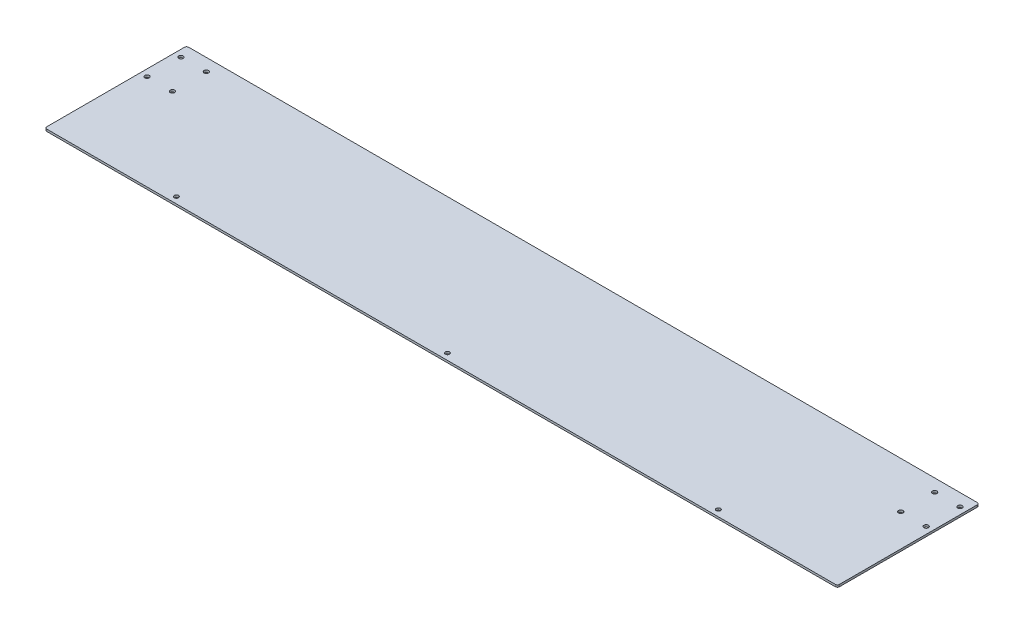
SolidWorks part; units mm, degrees
material "PC High Viscosity"
ref_plane "Front Plane" through (0, 0, 0) normal (0, 0, 1) x (1, 0, 0)
ref_plane "Top Plane" through (0, 0, 0) normal (0, 1, 0) x (1, 0, 0)
ref_plane "Right Plane" through (0, 0, 0) normal (1, 0, 0) x (0, 0, -1)
sketch "Sketch1" plane through (0, 0, 0) normal (0, 1, 0) x (1, 0, 0)
  line L1 (-591.185, -106.3625) -> (591.185, -106.3625)
  line L2 (-594.36, -103.1875) -> (-594.36, 103.1875)
  line L3 (-591.185, 106.3625) -> (591.185, 106.3625)
  line L4 (594.36, -103.1875) -> (594.36, 103.1875)
  line L5 (-594.36, -106.3625) -> (594.36, 106.3625) construction
  line L6 (-594.36, 106.3625) -> (594.36, -106.3625) construction
  arc A0 (591.185, 106.3625) -> (594.36, 103.1875) centre (591.185, 103.1875) cw
  arc A1 (591.185, -106.3625) -> (594.36, -103.1875) centre (591.185, -103.1875) ccw
  arc A2 (-591.185, -106.3625) -> (-594.36, -103.1875) centre (-591.185, -103.1875) cw
  arc A3 (-594.36, 103.1875) -> (-591.185, 106.3625) centre (-591.185, 103.1875) cw
  point P0 (0, 0)
  dimension "D3" = 3.175
  dimension "D1" = 1188.72
  dimension "D2" = 212.725
extrude "Boss-Extrude1" add sketch "Sketch1" along normal blind 3.175
sketch "Sketch2" plane through (0, 3.175, 0) normal (0, 1, 0) x (1, 0, 0)
  line L2 (-406.4, -96.8375) -> (406.4, -96.8375) construction
  line L3 (-591.185, -106.3625) -> (591.185, -106.3625) construction
  point P2 (0, -96.8375)
  point P12 (0, -96.8375)
  dimension "D1" = 812.8
  dimension "D3" = 9.525
hole_wizard "1/4 (0.25) Diameter Hole1" positions "Sketch3" profile "Sketch4" hole size "1/4" standard "ANSI Inch" end condition through all
sketch "Sketch3" plane through (0, 3.175, 0) normal (0, 1, 0) x (1, 0, 0)
  point P9 (0, -96.8375)
  point P28 (-406.4, -96.8375)
  point P31 (406.4, -96.8375)
sketch "Sketch4" plane through (0, 3.175, 96.8375) normal (1, 0, 0) x (0, 0, 1)
  line L0 (0, 0) -> (0, 3.175)
  line L1 (0, 3.175) -> (3.175, 3.175)
  line L2 (3.175, 3.175) -> (3.175, 0)
  line L5 (3.175, 0) -> (0, 0)
  line L11 (0, -6.35) -> (0, 107.95) construction
  dimension "Thru Hole Dia." = 6.35
  dimension "Thru Hole Depth" = 3.175
sketch "Sketch5" plane through (0, 3.175, 0) normal (0, 1, 0) x (1, 0, 0)
  line L0 (591.185, 106.3625) -> (-591.185, 106.3625) construction
  line L1 (584.2, 36.9087) -> (546.1, 36.9087) construction
  line L2 (584.2, 36.9087) -> (584.2, 87.7087) construction
  line L3 (584.2, 87.7087) -> (546.1, 87.7087) construction
  line L4 (546.1, 36.9087) -> (546.1, 87.7087) construction
  line L5 (584.2, 36.9087) -> (546.1, 87.7087) construction
  line L6 (584.2, 87.7087) -> (546.1, 36.9087) construction
  line L7 (-546.1, 36.9087) -> (-584.2, 36.9087) construction
  line L8 (-546.1, 36.9087) -> (-546.1, 87.7087) construction
  line L9 (-546.1, 87.7087) -> (-584.2, 87.7087) construction
  line L10 (-584.2, 36.9087) -> (-584.2, 87.7087) construction
  line L11 (-546.1, 36.9087) -> (-584.2, 87.7087) construction
  line L12 (-546.1, 87.7087) -> (-584.2, 36.9087) construction
  line L13 (594.36, -103.1875) -> (594.36, 103.1875) construction
  line L14 (-594.36, 103.1875) -> (-594.36, -103.1875) construction
  point P4 (565.15, 62.3087)
  point P9 (-565.15, 62.3087)
  dimension "D1" = 38.1
  dimension "D2" = 50.8
  dimension "D3" = 18.6538
  dimension "D4" = 10.16
  dimension "D5" = 10.16
hole_wizard "17/64 (0.26563) Diameter Hole2" positions "Sketch6" profile "Sketch7" hole size "17/64" standard "ANSI Inch" end condition through all
sketch "Sketch6" plane through (0, 3.175, 0) normal (0, 1, 0) x (1, 0, 0)
  point P0 (-546.1, 36.9087)
  point P3 (-546.1, 87.7087)
  point P6 (-584.2, 87.7087)
  point P9 (-584.2, 36.9087)
  point P12 (584.2, 36.9087)
  point P15 (546.1, 36.9087)
  point P18 (546.1, 87.7087)
  point P21 (584.2, 87.7087)
sketch "Sketch7" plane through (-546.1, 3.175, -36.9087) normal (1, 0, 0) x (0, 0, 1)
  line L0 (0, 0) -> (0, 3.175)
  line L1 (0, 3.175) -> (3.3735, 3.175)
  line L2 (3.3735, 3.175) -> (3.3735, 0)
  line L5 (3.3735, 0) -> (0, 0)
  line L11 (0, -6.35) -> (0, 107.95) construction
  dimension "Thru Hole Dia." = 6.747
  dimension "Thru Hole Depth" = 3.175
